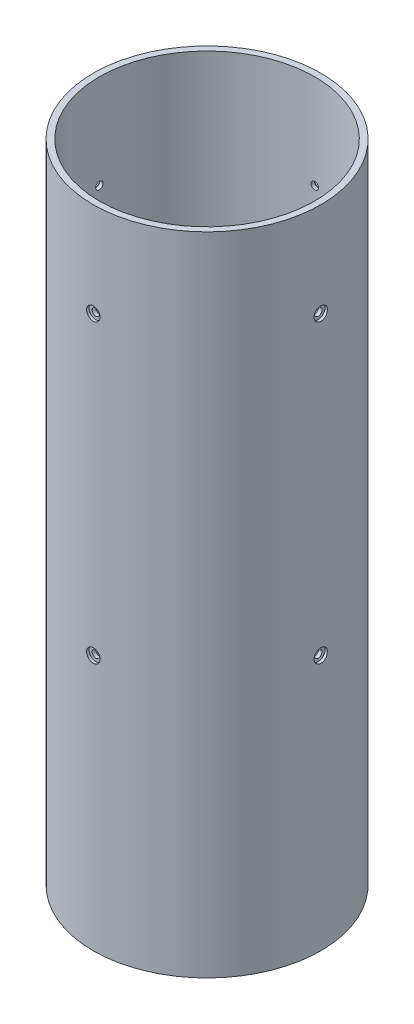
SolidWorks part; units mm, degrees
material "E-Glass Fiber"
ref_plane "Front Plane" through (0, 0, 0) normal (0, 0, 1) x (1, 0, 0)
ref_plane "Top Plane" through (0, 0, 0) normal (0, 1, 0) x (1, 0, 0)
ref_plane "Right Plane" through (0, 0, 0) normal (1, 0, 0) x (0, 0, -1)
sketch "Sketch1" plane through (0, 0, 0) normal (0, 1, 0) x (1, 0, 0)
  circle A0 centre (0, 0) radius 53.721
  circle A1 centre (0, 0) radius 50.8
  dimension "D1" = 107.442
  dimension "D2" = 101.6
extrude "Boss-Extrude1" add sketch "Sketch1" along normal blind 304.8
sketch "Sketch2" plane through (0, 0, 0) normal (0, 0, 1) x (1, 0, 0)
  line L2 (0, 0) -> (0, 120.65)
  circle A0 centre (0, 120.65) radius 1.7526
  dimension "D2" = 3.5052
  dimension "D1" = 120.65
extrude "Bulkhead Holes" cut sketch "Sketch2" against normal blind 127 contours A0
pattern_circular "CirPattern1" count 4 over 360 about axis through (0, 304.8, 0) along (0, -1, 0) of "Bulkhead Holes" reverse direction yes
ref_plane "Plane1" through (53.721, 0, 0) normal (1, 0, 0) x (0, 0, -1)
sketch "Sketch3" plane through (53.721, 0, 0) normal (1, 0, 0) x (0, 0, -1)
  line L0 (0, 0) -> (0, 304.8) construction
  line L1 (-53.721, 0) -> (53.721, 0) construction
  line L2 (50.8, 304.8) -> (-50.8, 304.8) construction
  line L3 (53.721, 304.8) -> (-53.721, 304.8) construction
  circle A0 centre (0, 260.35) radius 1.7526
  dimension "D1" = 3.5052
  dimension "D2" = 44.45
extrude "Cut-Extrude1" cut sketch "Sketch3" against normal up to next
pattern_circular "CirPattern2" count 4 over 360 about axis through (0, 304.8, 0) along (0, -1, 0) of "Cut-Extrude1"
sketch "Sketch4" plane through (53.721, 0, 0) normal (1, 0, 0) x (0, 0, -1)
  line L0 (0, 304.8) -> (0, 0) construction
  line L1 (53.721, 304.8) -> (-53.721, 304.8) construction
  line L2 (-53.721, 0) -> (53.721, 0) construction
  circle A0 centre (0, 260.35) radius 3.175
  circle A1 centre (0, 120.65) radius 3.175
  dimension "D1" = 6.35
  dimension "D2" = 6.35
extrude "Countersink Cut" cut sketch "Sketch4" against normal blind 1.27
pattern_circular "CirPattern3" count 4 over 360 about axis through (0, 304.8, 0) along (0, -1, 0) of "Countersink Cut" reverse direction yes
